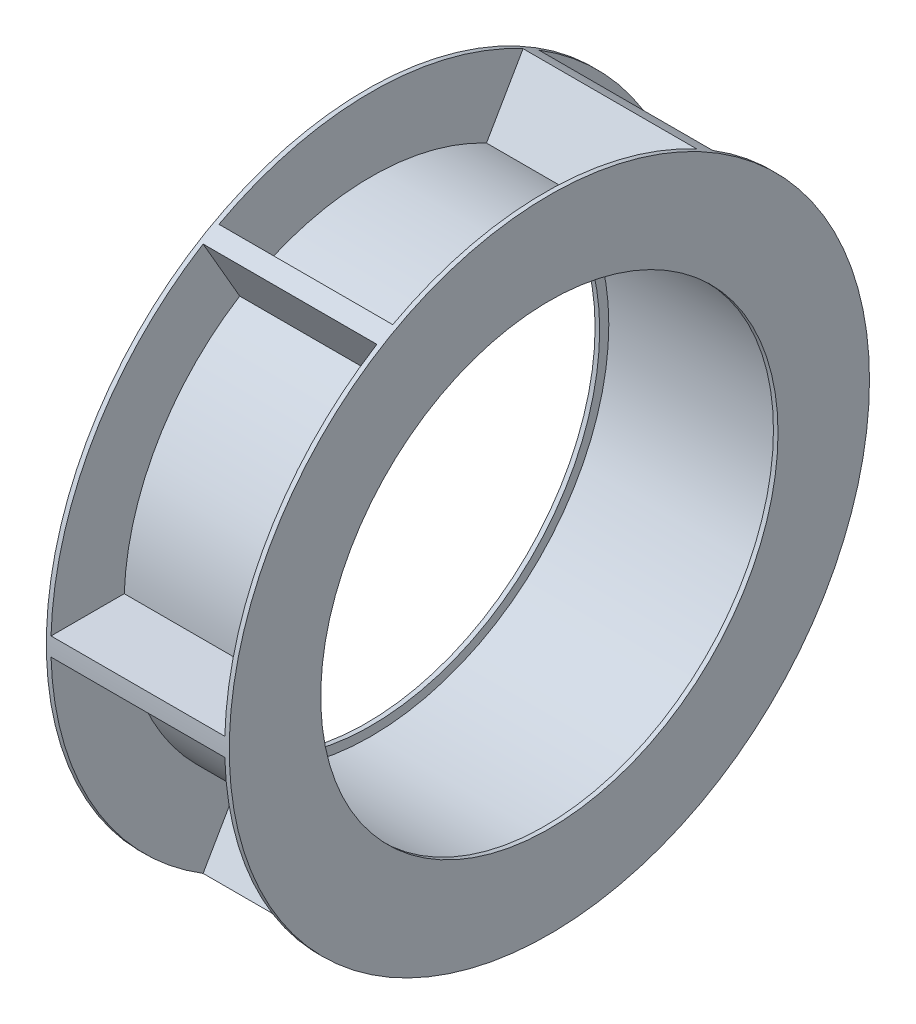
SolidWorks part; units mm, degrees
material "6061-T6 (SS)"
ref_plane "Front Plane" through (0, 0, 0) normal (1, 0, 0) x (0, 1, 0)
ref_plane "Top Plane" through (0, 0, 0) normal (0, 0, 1) x (0, 1, 0)
ref_plane "Right Plane" through (0, 0, 0) normal (0, 1, 0) x (-1, 0, 0)
sketch "Sketch8" plane through (0, 0, 0) normal (1, 0, 0) x (0, 1, 0)
  circle A0 centre (0, 0) radius 125
  circle A1 centre (0, 0) radius 175
  dimension "D1" = 250
  dimension "D2" = 50
extrude "Boss-Extrude7" add sketch "Sketch8" along normal mid plane 100
sketch "Sketch9" plane through (0, 0, 0) normal (1, 0, 0) x (0, 1, 0)
  circle A0 centre (0, 0) radius 125 construction
  circle A1 centre (0, 0) radius 125
  circle A2 centre (0, 0) radius 130
  dimension "D1" = 5
extrude "Cut-Extrude2" cut sketch "Sketch9" against normal mid plane 95
sketch "Sketch10" plane through (50, 0, 0) normal (1, 0, 0) x (0, 1, 0)
  line L0 (0, -1000) -> (0, 49000) construction
  line L1 (149.0544, 91.8301) -> (110, 69.282)
  line L2 (-5, 175) -> (5, 175)
  line L3 (-5, 175) -> (-5, 129.9038)
  line L4 (-5, 129.9038) -> (5, 129.9038)
  line L5 (5, 175) -> (5, 129.9038)
  line L6 (149.0544, 91.8301) -> (154.0544, 83.1699)
  line L7 (154.0544, 83.1699) -> (115, 60.6218)
  line L8 (110, 69.282) -> (115, 60.6218)
  line L9 (154.0544, -83.1699) -> (115, -60.6218)
  line L10 (154.0544, -83.1699) -> (149.0544, -91.8301)
  line L11 (149.0544, -91.8301) -> (110, -69.282)
  line L12 (115, -60.6218) -> (110, -69.282)
  line L13 (5, -175) -> (5, -129.9038)
  line L14 (5, -175) -> (-5, -175)
  line L15 (-5, -175) -> (-5, -129.9038)
  line L16 (5, -129.9038) -> (-5, -129.9038)
  line L17 (-149.0544, -91.8301) -> (-110, -69.282)
  line L18 (-149.0544, -91.8301) -> (-154.0544, -83.1699)
  line L19 (-154.0544, -83.1699) -> (-115, -60.6218)
  line L20 (-110, -69.282) -> (-115, -60.6218)
  line L21 (-154.0544, 83.1699) -> (-115, 60.6218)
  line L22 (-154.0544, 83.1699) -> (-149.0544, 91.8301)
  line L23 (-149.0544, 91.8301) -> (-110, 69.282)
  line L24 (-115, 60.6218) -> (-110, 69.282)
  circle A0 centre (0, 0) radius 175 construction
  circle A1 centre (0, 0) radius 175
  circle A3 centre (0, 0) radius 130 construction
  circle A4 centre (0, 0) radius 135
  point P35 (0, 0)
  circle M12 centre (0, 0) radius 175
  dimension "D4" = 260
  dimension "D5" = 260
  dimension "D1" = 10
  dimension "D2" = 6
  dimension "D3" = 5
extrude "Cut-Extrude3" cut sketch "Sketch10" against normal through all both and the other way through all contours A3 L1 L5 M12 | A3 L9 L7 M12 | A3 L13 L11 M12 | A3 L17 L15 M12 | A3 L21 L19 M12 | A3 L3 L23 M12 region at (50, 74.8569, 129.656) region at (50, 149.7138, 0) region at (50, -74.8569, 129.656) region at (50, 74.8569, -129.656) region at (50, -149.7138, 0) region at (50, -74.8569, -129.656)
sketch "Sketch11" plane through (50, 0, 0) normal (1, 0, 0) x (0, 1, 0)
  circle A0 centre (0, 0) radius 125 construction
  circle A1 centre (0, 0) radius 125
  circle A2 centre (0, 0) radius 175
  dimension "D1" = 250
extrude "Boss-Extrude8" add sketch "Sketch11" against normal blind 2.5
mirror "Mirror3" about plane through (0, 0, 0) normal (1, 0, 0) of "Boss-Extrude8"
sketch "Sketch2" plane through (0, 0, 0) normal (1, 0, 0) x (0, 1, 0)
  line L0 (0, -1000) -> (0, 125) construction
  line L8 (-7.5, 23.8485) -> (-7.5, 125)
  line L9 (-7.5, 125) -> (7.5, 125)
  line L10 (7.5, 23.8485) -> (7.5, 125)
  line L11 (20.3636, 14.5025) -> (116.5644, 45.76)
  line L13 (24.9989, 0.2367) -> (121.1997, 31.4942)
  line L14 (116.5644, 45.76) -> (121.1997, 31.4942)
  line L15 (20.0854, -14.8854) -> (79.5408, -96.7187)
  line L17 (7.9502, -23.7022) -> (67.4055, -105.5355)
  line L18 (79.5408, -96.7187) -> (67.4055, -105.5355)
  line L19 (-7.9502, -23.7022) -> (-67.4055, -105.5355)
  line L21 (-20.0854, -14.8854) -> (-79.5408, -96.7187)
  line L22 (-67.4055, -105.5355) -> (-79.5408, -96.7187)
  line L23 (-24.9989, 0.2367) -> (-121.1997, 31.4942)
  line L25 (-20.3636, 14.5025) -> (-116.5644, 45.76)
  line L26 (-121.1997, 31.4942) -> (-116.5644, 45.76)
  line L31 (-962.4087, -312.7056) -> (118.8821, 38.6271) construction
  circle A0 centre (0, 0) radius 10
  circle A7 centre (0, 0) radius 25
  point P17 (0, 125)
  point P40 (0, 0)
  dimension "D1" = 20
  dimension "D2" = 50
  dimension "D3" = 125
  dimension "D4" = 15
  dimension "D6" = 125
  dimension "D5" = 5
extrude "Boss-Extrude1" [suppressed] add sketch "Sketch2" along normal mid plane 100
sketch "Sketch4" [suppressed] plane through (50, 0, 0) normal (1, 0, 0) x (0, 1, 0)
  line L0 (0, -1000) -> (0, 49000) construction
  line L1 (-1000, 0) -> (49000, 0) construction
  line L3 (-7.5, 125) -> (7.5, 125) construction
  circle A4 centre (0, 0) radius 125
  circle A5 centre (0, 0) radius 165
  dimension "D1" = 330
extrude "Boss-Extrude3" [suppressed] add sketch "Sketch4" against normal up to surface (100 mm away)
sketch "Sketch5" [suppressed] plane through (50, 0, 0) normal (1, 0, 0) x (0, 1, 0)
  line L0 (0, -1000) -> (0, 49000) construction
  line L34 (114.8915, 118.427) -> (90.1257, 93.6613)
  line L35 (-2.5, 165) -> (2.5, 165)
  line L36 (-2.5, 165) -> (-2.5, 129.976)
  line L37 (-2.5, 129.976) -> (2.5, 129.976)
  line L38 (2.5, 165) -> (2.5, 129.976)
  line L39 (114.8915, 118.427) -> (118.427, 114.8915)
  line L40 (118.427, 114.8915) -> (93.6613, 90.1257)
  line L41 (90.1257, 93.6613) -> (93.6613, 90.1257)
  line L42 (164.9677, 2.4866) -> (129.9436, 2.4866)
  line L43 (164.9677, 2.4866) -> (164.9677, -2.5134)
  line L44 (164.9677, -2.5134) -> (129.9436, -2.5134)
  line L45 (129.9436, 2.4866) -> (129.9436, -2.5134)
  line L46 (118.3947, -114.9049) -> (93.6289, -90.1391)
  line L47 (118.3947, -114.9049) -> (114.8591, -118.4404)
  line L48 (114.8591, -118.4404) -> (90.0934, -93.6746)
  line L49 (93.6289, -90.1391) -> (90.0934, -93.6746)
  line L50 (2.4543, -164.9811) -> (2.4543, -129.957)
  line L51 (2.4543, -164.9811) -> (-2.5457, -164.9811)
  line L52 (-2.5457, -164.9811) -> (-2.5457, -129.957)
  line L53 (2.4543, -129.957) -> (-2.5457, -129.957)
  line L54 (-114.9372, -118.4081) -> (-90.1714, -93.6423)
  line L55 (-114.9372, -118.4081) -> (-118.4727, -114.8725)
  line L56 (-118.4727, -114.8725) -> (-93.707, -90.1068)
  line L57 (-90.1714, -93.6423) -> (-93.707, -90.1068)
  line L58 (-165.0134, -2.4677) -> (-129.9894, -2.4677)
  line L59 (-165.0134, -2.4677) -> (-165.0134, 2.5323)
  line L60 (-165.0134, 2.5323) -> (-129.9894, 2.5323)
  line L61 (-129.9894, -2.4677) -> (-129.9894, 2.5323)
  line L62 (-118.4404, 114.9238) -> (-93.6746, 90.1581)
  line L63 (-118.4404, 114.9238) -> (-114.9049, 118.4593)
  line L64 (-114.9049, 118.4593) -> (-90.1391, 93.6936)
  line L65 (-93.6746, 90.1581) -> (-90.1391, 93.6936)
  circle A1 centre (0, 0) radius 130
  arc A3 (116.3503, 45.6905) -> (7.5, 124.7748) centre (0, 0) ccw construction
  circle A4 centre (0, 0) radius 165 construction
  circle A5 centre (0, 0) radius 165
  point P44 (-0.0229, 0.0095)
  dimension "D1" = 5
  dimension "D2" = 5
  dimension "D3" = 8
extrude "Cut-Extrude1" [suppressed] cut sketch "Sketch5" against normal blind 120
sketch "Sketch7" [suppressed] plane through (50, 0, 0) normal (1, 0, 0) x (0, 1, 0)
  circle A3 centre (0, 0) radius 130
  arc A4 (129.9762, 2.4866) -> (93.6746, 90.1391) centre (0, 0) ccw construction
  circle A5 centre (0, 0) radius 165
extrude "Boss-Extrude6" [suppressed] add sketch "Sketch7" against normal blind 4
mirror "Mirror2" [suppressed] about plane through (0, 0, 0) normal (1, 0, 0)
sketch "Sketch6" [suppressed] plane through (60, 0, 0) normal (1, 0, 0) x (0, 1, 0)
  line L0 (-14.4338, 25) -> (-28.8675, 0) construction
  line L1 (-28.8675, 0) -> (-14.4338, -25) construction
  line L2 (-14.4338, -25) -> (14.4338, -25) construction
  line L3 (14.4338, -25) -> (28.8675, 0) construction
  line L4 (28.8675, 0) -> (14.4338, 25) construction
  line L5 (14.4338, 25) -> (-14.4338, 25) construction
  line L6 (-14.4338, 25) -> (-28.8675, 0)
  line L7 (-28.8675, 0) -> (-14.4338, -25)
  line L8 (-14.4338, -25) -> (14.4338, -25)
  line L9 (14.4338, -25) -> (28.8675, 0)
  line L10 (28.8675, 0) -> (14.4338, 25)
  line L11 (14.4338, 25) -> (-14.4338, 25)
  circle A0 centre (0, 0) radius 150
extrude "Boss-Extrude4" [suppressed] add sketch "Sketch6" along normal blind 4
mirror "Mirror1" [suppressed] about plane through (0, 0, 0) normal (1, 0, 0)
